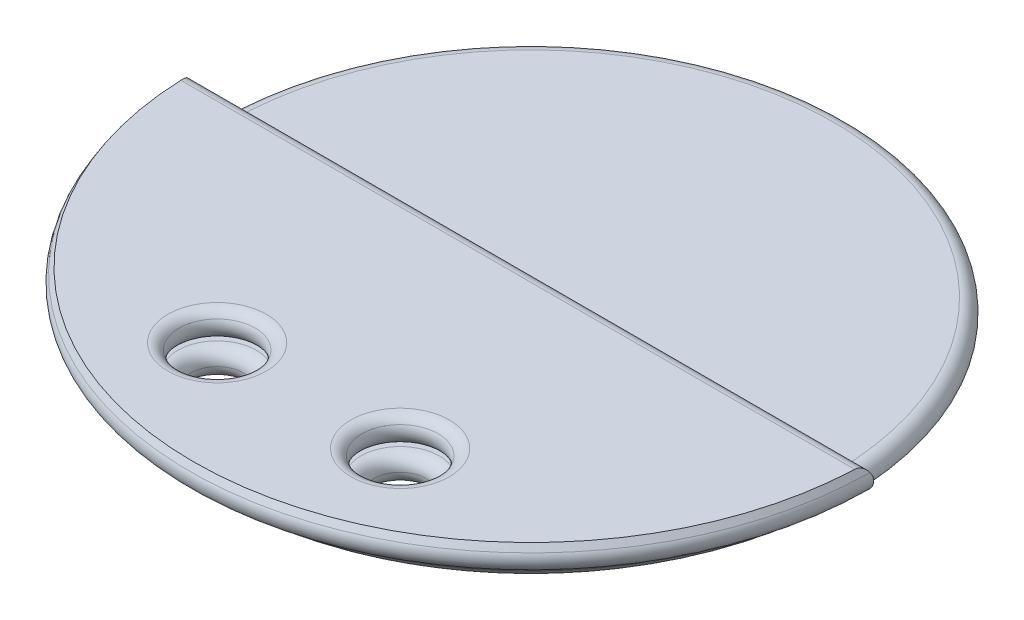
SolidWorks part; units mm, degrees
ref_plane "Front Plane" through (0, 0, 0) normal (0, 0, 1) x (1, 0, 0)
ref_plane "Top Plane" through (0, 0, 0) normal (0, 1, 0) x (1, 0, 0)
ref_plane "Right Plane" through (0, 0, 0) normal (1, 0, 0) x (0, 0, -1)
sketch "Sketch1" plane through (0, 0, 0) normal (0, 1, 0) x (1, 0, 0)
  line L0 (0, 0) -> (0, -27) construction
  line L1 (0, -27) -> (0, -17) construction
  line L2 (-7, -17) -> (7, -17)
  circle A0 centre (0, 0) radius 25
  circle A1 centre (0, 0) radius 27
  circle A2 centre (-7, -17) radius 2
  circle A3 centre (7, -17) radius 2
  point P9 (0, -17)
  dimension "D1" = 54
  dimension "D2" = 50
  dimension "D5" = 4
  dimension "D6" = 4
  dimension "D3" = 10
  dimension "D4" = 14
extrude "Boss-Extrude1" add sketch "Sketch1" along normal blind 2 draft 31 contours A1 A0 | A0 A3 A2 region at (0, 0, -0.2204) region at (-26.2363, 0, 0)
fillet "Fillet1" radius 1 4 edges at (-7, 0, 19) (7, 0, 19) (7, 2, 20.2017) (-7, 2, 20.2017)
sketch "Sketch3" plane through (0, 0, 0) normal (0, 1, 0) x (1, 0, 0)
  line L0 (0, 0) -> (25.7983, 0) construction
  line L1 (25.7983, 0) -> (-25.7983, 0) construction
  line L2 (27, 0) -> (-27, 0)
  circle A0 centre (0, 0) radius 25.7983 construction
  circle A1 centre (0, 0) radius 27
  circle A2 centre (0, 0) radius 25
  point P11 (0, 0)
  dimension "D1" = 50
extrude "Boss-Extrude2" add sketch "Sketch3" against normal blind 2 draft 32 contours L2 A2 | L2 A2 region at (0, 0, 10.6103) region at (0, 0, -10.6103)
sketch "Sketch5" plane through (0, 0, 0) normal (0, 1, 0) x (1, 0, 0)
  line L0 (0, 27) -> (0, -27) construction
  line L1 (0, -27) -> (0, -17) construction
  line L2 (-7, -17) -> (7, -17)
  circle A0 centre (0, 0) radius 27 construction
  circle A1 centre (-7, -17) radius 2
  circle A2 centre (7, -17) radius 2
  point P9 (0, -17)
  dimension "D3" = 4
  dimension "D4" = 4
  dimension "D1" = 10
  dimension "D2" = 14
extrude "Cut-Extrude1" cut sketch "Sketch5" against normal mid plane 10 contours A1 | A2 region at (7, 0, 15.0566) region at (-8.9434, 0, 17)
fillet "Fillet2" radius 1 4 edges at (7, 0, 19) (7, -2, 19) (-7, -2, 19) (-7, 0, 19)
ref_plane "Plane1" through (0, 2, 0) normal (0, 1, 0) x (1, 0, 0)
sketch "Sketch7" plane through (0, 2, 0) normal (0, 1, 0) x (1, 0, 0)
  line L0 (0, 0) -> (27, 0)
  line L1 (0, 0) -> (-27, 0)
  circle A0 centre (0, 0) radius 27 construction
  arc A1 (27, 0) -> (-27, 0) centre (0, 0) ccw
extrude "Cut-Extrude3" cut sketch "Sketch7" against normal blind 2
fillet "Fillet3" radius 1 2 edges at (0, 0, -25) (0, 2, 0)
fillet "Fillet4" radius 1 1 edges at (0, 0, 27)
fillet "Fillet6" radius 3 1 edges at (0, -2, 23.7503)
fillet "Fillet7" radius 3 1 edges at (0, 0, 25)
